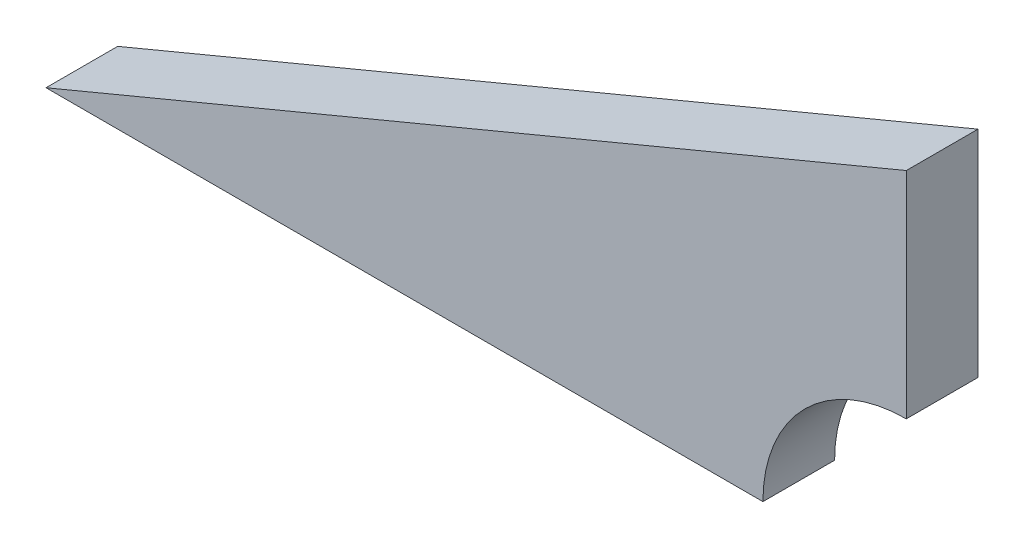
SolidWorks part; units mm, degrees
material "1.0037 (S235JR)"
ref_plane "E_Rechts" through (0, 0, 0) normal (0, 0, 1) x (1, 0, 0)
ref_plane "E_Oben" through (0, 0, 0) normal (0, 1, 0) x (1, 0, 0)
ref_plane "E_Vorne" through (0, 0, 0) normal (1, 0, 0) x (0, 0, -1)
sketch "Skizze1" plane through (0, 0, 0) normal (0, 0, 1) x (1, 0, 0)
  line L1 (0, 20) -> (0, 50)
  line L2 (0, -55) -> (0, 55) construction
  line L3 (0, 50) -> (-120, 0)
  line L4 (55, 0) -> (-55, 0) construction
  line L5 (-120, 0) -> (-20, 0)
  arc A0 (0, 20) -> (-20, 0) centre (0, 0) ccw
  dimension "D3" = 40
  dimension "D1" = 50
  dimension "D2" = 120
extrude "Aufsatz-Linear austragen1" add sketch "Skizze1" along normal mid plane 10
